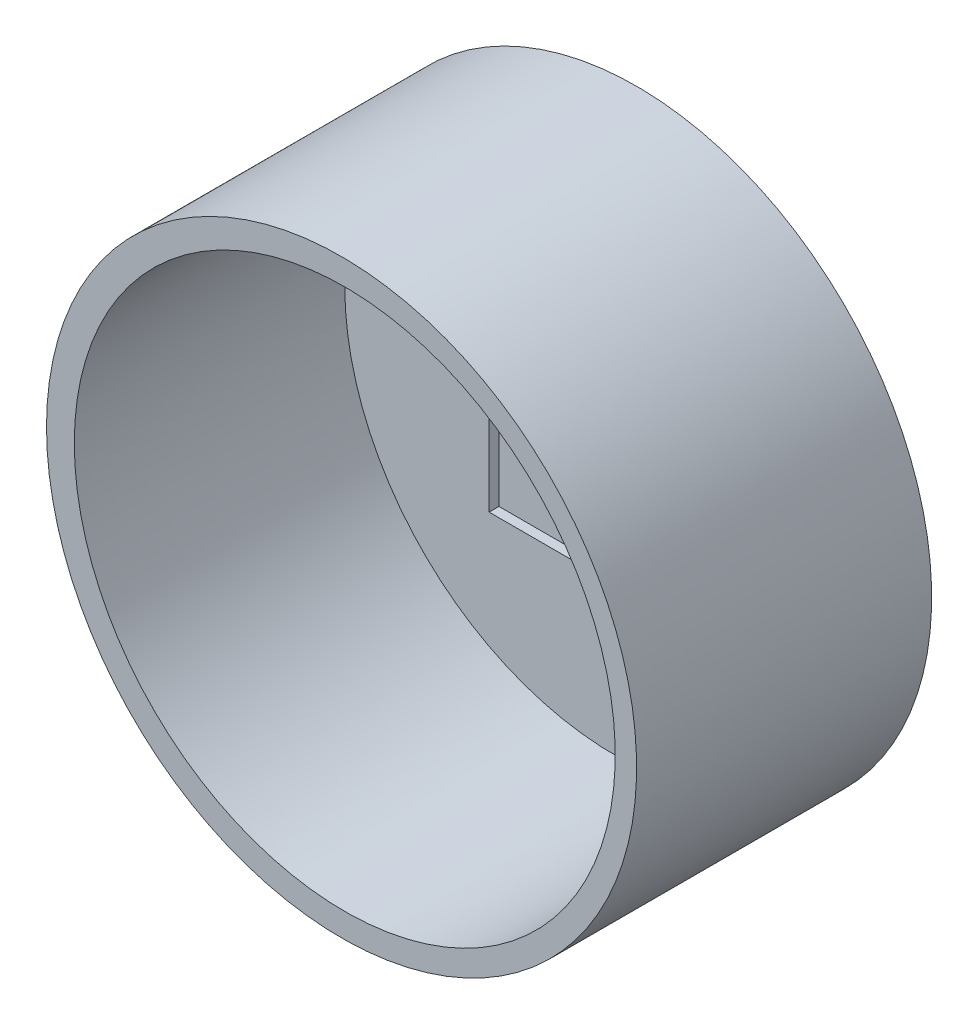
SolidWorks part; units mm, degrees
material "AISI 1020"
ref_plane "Front Plane" through (0, 0, 0) normal (0, 0, 1) x (1, 0, 0)
ref_plane "Top Plane" through (0, 0, 0) normal (0, 1, 0) x (1, 0, 0)
ref_plane "Right Plane" through (0, 0, 0) normal (1, 0, 0) x (0, 0, -1)
sketch "Sketch1" plane through (0, 0, 0) normal (0, 0, 1) x (1, 0, 0)
  circle A0 centre (0, 0) radius 76.2
  circle A1 centre (0.8288, 0) radius 69.85
  dimension "D1" = 152.4
  dimension "D2" = 139.7
extrude "Boss-Extrude1" add sketch "Sketch1" along normal blind 76.2
sketch "Sketch3" plane through (0, 0, 0) normal (0, 0, 1) x (1, 0, 0)
  circle A0 centre (0, 0) radius 76.2
extrude "Boss-Extrude2" add sketch "Sketch3" along normal blind 6.35
sketch "Sketch4" plane through (0, 0, 6.35) normal (0, 0, 1) x (1, 0, 0)
  line L1 (-31.75, 31.75) -> (31.75, 31.75)
  line L2 (-31.75, 31.75) -> (-31.75, -31.75)
  line L3 (-31.75, -31.75) -> (31.75, -31.75)
  line L4 (31.75, 31.75) -> (31.75, -31.75)
  point P5 (0, 31.75)
  point P7 (-31.75, 0)
  dimension "D1" = 63.5
  dimension "2.5" = 63.5
extrude "Cut-Extrude1" cut sketch "Sketch4" against normal blind 2.54
sketch "Sketch5" plane through (0, 0, 6.35) normal (0, 0, 1) x (1, 0, 0)
  line L0 (-31.75, 31.75) -> (-31.75, -31.75) construction
  line L1 (31.75, 31.75) -> (-31.75, 31.75) construction
  line L2 (31.75, -31.75) -> (31.75, 31.75) construction
  line L3 (-31.75, -31.75) -> (31.75, -31.75) construction
  circle A0 centre (0, 44.163) radius 2.54
  circle A1 centre (44.163, 0) radius 2.54
  circle A2 centre (-44.163, 0) radius 2.54
  circle A3 centre (0, -44.163) radius 2.54
  dimension "D1" = 5.08
  dimension "D2" = 5.08
  dimension "D3" = 5.08
  dimension "D4" = 5.08
  dimension "D5" = 12.413
  dimension "D6" = 12.413
  dimension "D7" = 12.413
  dimension "D8" = 12.413
extrude "Cut-Extrude2" cut sketch "Sketch5" against normal through all
